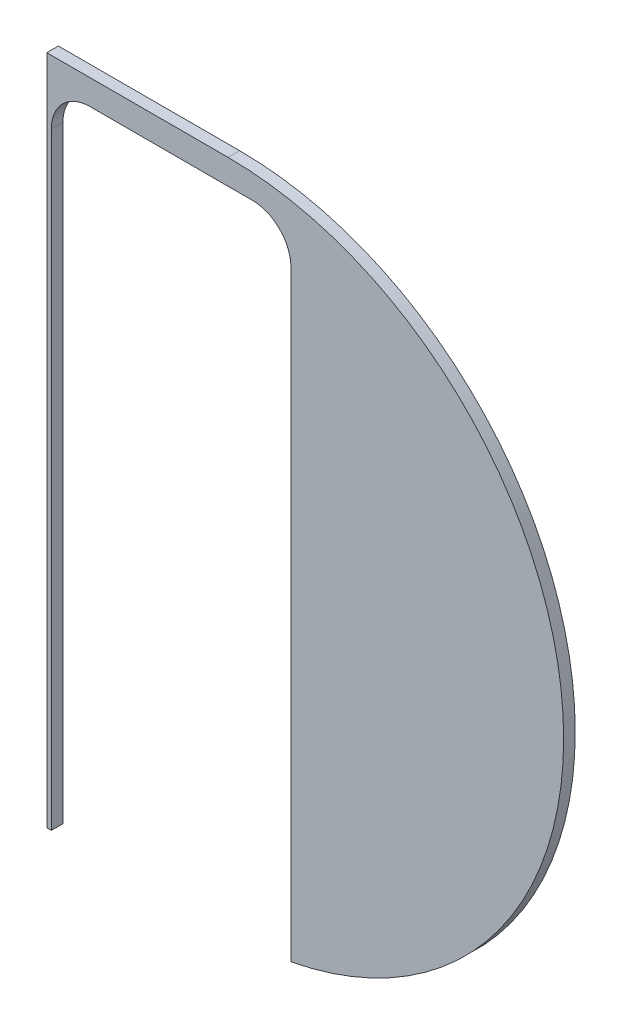
SolidWorks part; units mm, degrees
ref_plane "Front Plane" through (0, 0, 0) normal (0, 0, 1) x (1, 0, 0)
ref_plane "Top Plane" through (0, 0, 0) normal (0, 1, 0) x (1, 0, 0)
ref_plane "Right Plane" through (0, 0, 0) normal (1, 0, 0) x (0, 0, -1)
sketch "Sketch1" plane through (0, 0, 0) normal (0, 0, 1) x (1, 0, 0)
  line L1 (0, 0) -> (470, 0)
  line L2 (0, 0) -> (0, 1740)
  line L3 (0, 1740) -> (470, 1740)
  line L4 (470, 0) -> (470, 1740) construction
  arc A0 (470, 1740) -> (470, 0) centre (470, 870) cw
  dimension "D1" = 470
  dimension "D2" = 1740
extrude "Boss-Extrude1" add sketch "Sketch1" along normal blind 30
extrude "Cut-Extrude5" cut sketch "Sketch6" against normal blind 330
sketch "Sketch6" plane through (-1354.1121, -994.4575, -2) normal (0, 0, -1) x (-1, 0, 0)
  line L1 (-1887.1121, 819.4575) -> (-1466.1121, 819.4575)
  line L2 (-1987.1121, 919.4575) -> (-1987.1121, 2569.4575)
  line L3 (-1887.1121, 2669.4575) -> (-1466.1121, 2669.4575)
  line L4 (-1366.1121, 919.4575) -> (-1366.1121, 2569.4575)
  arc A0 (-1466.1121, 819.4575) -> (-1366.1121, 919.4575) centre (-1466.1121, 919.4575) ccw
  arc A1 (-1887.1121, 819.4575) -> (-1987.1121, 919.4575) centre (-1887.1121, 919.4575) cw
  arc A2 (-1466.1121, 2669.4575) -> (-1366.1121, 2569.4575) centre (-1466.1121, 2569.4575) cw
  arc A3 (-1987.1121, 2569.4575) -> (-1887.1121, 2669.4575) centre (-1887.1121, 2569.4575) cw
